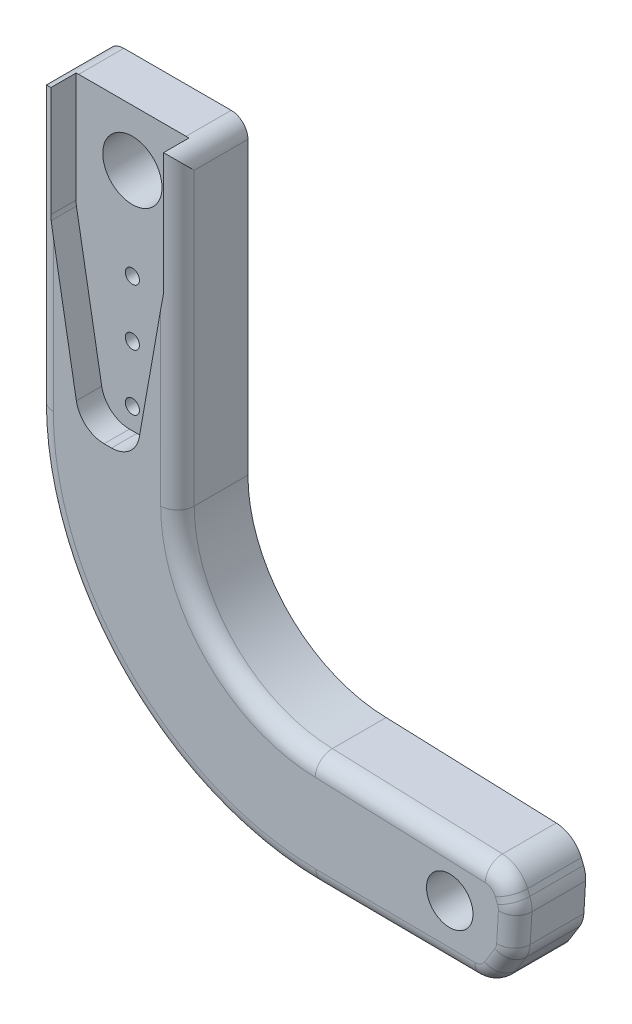
SolidWorks part; units mm, degrees
ref_plane "Front Plane" through (0, 0, 0) normal (0, 0, 1) x (1, 0, 0)
ref_plane "Top Plane" through (0, 0, 0) normal (0, 1, 0) x (1, 0, 0)
ref_plane "Right Plane" through (0, 0, 0) normal (1, 0, 0) x (0, 0, -1)
sketch "Sketch1" plane through (0, 0, 0) normal (0, 0, 1) x (1, 0, 0)
  line L0 (-5, 15.91) -> (5, 15.91) construction
  line L1 (-5, -19.91) -> (5, -19.91)
  line L2 (-5, -19.91) -> (-5, 19.91)
  line L3 (-5, 19.91) -> (5, 19.91)
  line L4 (5, -19.91) -> (5, 19.91)
  line L5 (-5, -19.91) -> (5, 19.91) construction
  line L6 (-5, 19.91) -> (5, -19.91) construction
  line L11 (-5, -19.91) -> (31.82, -19.91)
  line L12 (-5, -19.91) -> (-5, -11.91)
  line L13 (-5, -11.91) -> (31.82, -11.91)
  line L14 (31.82, -19.91) -> (31.82, -11.91)
  line L15 (0, -19.91) -> (0, 19.91) construction
  point P0 (0, 0)
  dimension "D1" = 10
  dimension "D2" = 39.82
  dimension "D3" = 8
  dimension "D4" = 36.82
  dimension "D5" = 4
extrude "Boss-Extrude1" add sketch "Sketch1" along normal blind 5 contours L2 L13 L4 L3 | L13 L2 L1 L4 | L11 L14 L13 L4 region at (0, -15.91, 0) region at (18.41, -15.91, 0) region at (0, 4, 0)
chamfer "Chamfer1" distance 3 angle 80 1 edges at (31.82, -11.91, 2.5) first distance on face at (31.82, -15.91, 2.5)
chamfer "Chamfer2" distance 17 angle 10 1 edges at (31.82, -19.91, 2.5) first distance on face at (13.41, -19.91, 2.5)
fillet "Fillet1" radius 1 2 edges at (31.82, -14.91, 2.5) (31.82, -16.9124, 2.5)
fillet "Fillet2" radius 10 1 edges at (5, -11.91, 2.5)
fillet "Fillet3" radius 20 1 edges at (-5, -19.91, 2.5)
sketch "Sketch2" plane through (0, 0, 5) normal (0, 0, 1) x (1, 0, 0)
  line L0 (0, 0) -> (0, 19.91) construction
  line L1 (-5, 19.91) -> (5, 19.91) construction
  line L2 (31.82, -15.9112) -> (0, -15.9112) construction
  line L3 (31.82, -16.0733) -> (31.82, -15.7491) construction
  line L4 (0, -15.9112) -> (0, 15.91) construction
  line L5 (0, 15.91) -> (31.82, -15.9112) construction
  circle A0 centre (0, 15.91) radius 2.06
  dimension "D1" = 4.12
  dimension "D2" = 4
sketch "Sketch3" plane through (0, 0, 0) normal (0, 0, -1) x (-1, 0, 0)
  line L0 (0, 19.91) -> (0, -15.9112) construction
  line L1 (0, -15.9112) -> (-31.82, -16.0733) construction
  line L2 (-31.82, -16.0733) -> (0, 15.91) construction
  circle A0 centre (0, 15.91) radius 2.1
  dimension "D1" = 4.2
sketch "Sketch4" plane through (0, 0, 5) normal (0, 0, 1) x (1, 0, 0)
  line L0 (0, 0) -> (0, 19.91) construction
  line L1 (-5, 19.91) -> (5, 19.91) construction
  circle A1 centre (0, 9.41) radius 0.5
  circle A2 centre (0, 5.41) radius 0.5
  circle A3 centre (0, 1.41) radius 0.5
  dimension "D2" = 1
  dimension "D3" = 1
  dimension "D4" = 10.5
  dimension "D5" = 4
  dimension "D6" = 1
  dimension "D7" = 4
extrude "Cut-Extrude1" cut sketch "Sketch4" against normal through all
sketch "Sketch5" plane through (0, 0, 5) normal (0, 0, 1) x (1, 0, 0)
  line L0 (-5, 19.91) -> (5, 19.91) construction
  line L1 (-4, 19.91) -> (4, 19.91)
  line L2 (-4, 19.91) -> (-4, -0.09)
  line L3 (-4, -0.09) -> (4, -0.09)
  line L4 (4, 19.91) -> (4, -0.09)
  line L5 (0, 0) -> (0, 19.91) construction
  dimension "D1" = 20
  dimension "D2" = 8
  dimension "D3" = 4
extrude "Cut-Extrude2" cut sketch "Sketch5" against normal blind 1.8
chamfer "Chamfer3" distance 12 angle 10 1 edges at (-4, -0.09, 4.1) first distance on face at (-4, 9.91, 4.1)
chamfer "Chamfer4" distance 2 angle 80 1 edges at (4, -0.09, 4.1) first distance on face at (1.058, -0.09, 4.1)
fillet "Fillet4" radius 2 4 edges at (-4, 11.91, 4.1) (4, 11.2526, 4.1) (2, -0.09, 4.1) (-1.8841, -0.09, 4.1)
extrude "Cut-Extrude3" cut sketch "Sketch3" against normal through all
sketch "Sketch6" plane through (0, 0, 5) normal (0, 0, 1) x (1, 0, 0)
  line L0 (14.8062, -11.91) -> (28.1662, -12.3978)
  line L1 (28.1662, -12.3978) -> (29.6636, -16.0637)
  line L2 (29.6636, -16.0637) -> (27.216, -20.0097)
  line L3 (27.216, -20.0097) -> (14.82, -19.91)
  line L4 (14.82, -19.91) -> (14.8062, -11.91)
  dimension "D1" = 87.81
  dimension "D2" = 13.36
  dimension "D3" = 114.31
  dimension "D4" = 125.97
  dimension "D5" = 121.35
  dimension "D6" = 3.96
extrude "Boss-Extrude2" add sketch "Sketch6" against normal blind 5
sketch "Sketch7" plane through (0, 0, 5) normal (0, 0, 1) x (1, 0, 0)
  line L0 (28.9884, -14.4107) -> (28.8077, -17.4436)
  line L1 (28.8077, -17.4436) -> (31.8076, -18.8774)
  line L2 (31.8076, -18.8774) -> (35.9706, -13.666)
  line L3 (35.9706, -13.666) -> (30.8329, -13.2063)
  line L4 (30.8329, -13.2063) -> (28.9884, -14.4107)
extrude "Cut-Extrude4" cut sketch "Sketch7" against normal blind 5
sketch "Sketch8" plane through (0, 0, 5) normal (0, 0, 1) x (1, 0, 0)
  line L0 (31.82, -15.9112) -> (0, -15.9112) construction
  circle A0 centre (24.32, -15.9112) radius 1.65
  dimension "D1" = 3.3
  dimension "D2" = 7.5
extrude "Cut-Extrude5" cut sketch "Sketch8" against normal blind 5
fillet "Fillet5" radius 2 4 edges at (28.1662, -12.3978, 2.5) (28.9884, -14.4107, 2.5) (28.8077, -17.4436, 2.5) (27.216, -20.0097, 2.5)
fillet "Fillet6" radius 1.19 15 edges at (-5, 9.9996, 5) (0.7944, -13.9892, 5) (20.4563, -19.9553, 5) (27.0741, -19.7523, 5) (28.1746, -18.4643, 5) (28.7476, -17.4245, 5) (28.8996, -15.9016, 5) (28.938, -14.4191, 5) (28.7354, -13.7913, 5) (27.9482, -12.7097, 5) (7.8607, -8.9141, 5) (20.841, -12.1303, 5) (5, 8.9991, 5) (-5, 19.91, 2.5) (5, 19.91, 2.5)
